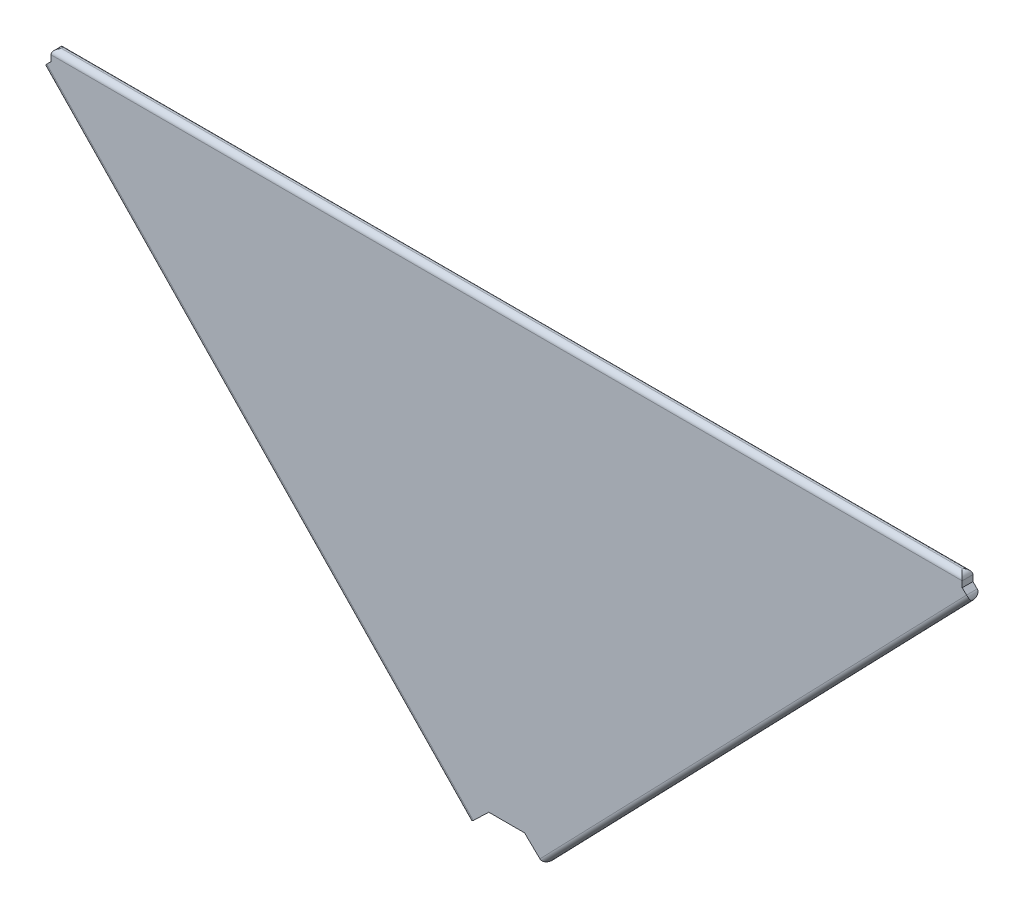
SolidWorks part; units mm, degrees
ref_plane "前视基准面" through (0, 0, 0) normal (0, 0, 1) x (1, 0, 0)
ref_plane "上视基准面" through (0, 0, 0) normal (0, 1, 0) x (1, 0, 0)
ref_plane "右视基准面" through (0, 0, 0) normal (1, 0, 0) x (0, 0, -1)
sketch "草图1" plane through (0, 0, 0) normal (0, 0, 1) x (1, 0, 0)
  line L0 (0, 0) -> (18.0611, 0)
  line L1 (18.0611, 0) -> (9.0306, -9.3514)
  line L2 (9.0306, -9.3514) -> (0, 0)
  line L3 (8.3359, -8.6321) -> (8.6956, -8.2847)
  line L4 (9.3655, -8.2847) -> (9.7252, -8.6321)
  line L5 (0.3473, -0.3597) -> (0.5, -0.2122)
  line L6 (0.5, -0.2122) -> (0.5, 0)
  line L7 (17.5611, 0) -> (17.5611, -0.2122)
  line L8 (17.5611, -0.2122) -> (17.7138, -0.3597)
  line L9 (8.6956, -8.2847) -> (9.3655, -8.2847)
  dimension "D1" = 13
  dimension "D2" = 46
  dimension "D3" = 13
  dimension "D4" = 0.5
  dimension "D5" = 0.5
  dimension "D6" = 0.5
  dimension "D7" = 0.5
  dimension "D8" = 1
  dimension "D9" = 1
extrude "凸台-拉伸1" add sketch "草图1" along normal blind 0.2 contours L8 L7 L0 L6 L5 L2 L3 L4 L1 region at (9.0306, -3.0673, 0)
fillet "圆角1" radius 0.1 12 edges at (17.5611, 0, 0.1) (9.0306, 0, 0.2) (0.5, 0, 0.1) (9.0306, 0, 0) (0.3473, -0.3597, 0.1) (4.3416, -4.4959, 0.2) (8.3359, -8.6321, 0.1) (4.3416, -4.4959, 0) (9.7252, -8.6321, 0.1) (13.7195, -4.4959, 0.2) (17.7138, -0.3597, 0.1) (13.7195, -4.4959, 0)
